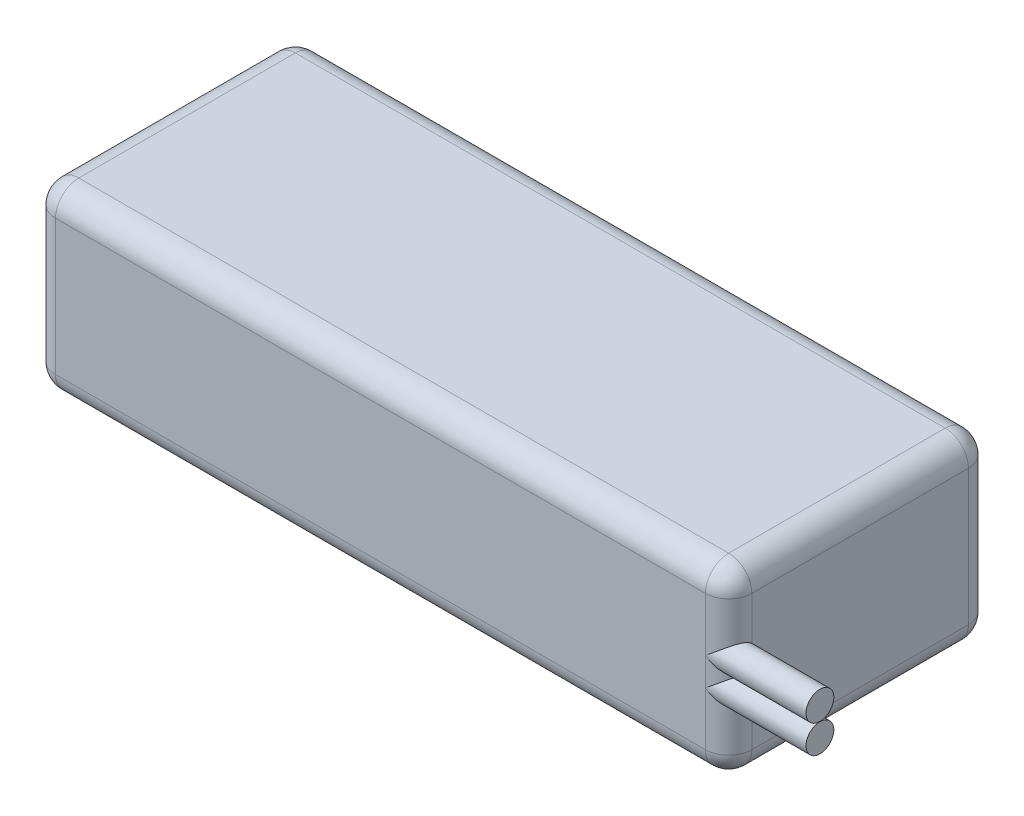
SolidWorks part; units mm, degrees
ref_plane "Front Plane" through (0, 0, 0) normal (0, 0, 1) x (1, 0, 0)
ref_plane "Top Plane" through (0, 0, 0) normal (0, 1, 0) x (1, 0, 0)
ref_plane "Right Plane" through (0, 0, 0) normal (1, 0, 0) x (0, 0, -1)
sketch "Sketch1" plane through (0, 0, 0) normal (0, 1, 0) x (1, 0, 0)
  line L1 (-42.6514, 15.3132) -> (47.3486, 15.3132)
  line L2 (-42.6514, 15.3132) -> (-42.6514, -18.6868)
  line L3 (-42.6514, -18.6868) -> (47.3486, -18.6868)
  line L4 (47.3486, 15.3132) -> (47.3486, -18.6868)
  dimension "D1" = 90
  dimension "D2" = 34
extrude "Boss-Extrude1" add sketch "Sketch1" along normal blind 23.5
sketch "Sketch2" plane through (47.3486, 0, 0) normal (1, 0, 0) x (0, 0, -1)
  line L0 (-18.6868, 23.5) -> (-18.6868, 0) construction
  line L1 (15.3132, 11.75) -> (-18.6868, 11.75) construction
  line L2 (15.3132, 23.5) -> (15.3132, 0) construction
  circle A0 centre (-16.8868, 13.57) radius 1.8
  circle A1 centre (-16.8868, 9.93) radius 1.8
  dimension "D1" = 3.6
  dimension "D2" = 1.82
  dimension "D3" = 1.82
extrude "Boss-Extrude4" add sketch "Sketch2" along normal blind 10
fillet "Fillet1" radius 3 14 edges at (-42.6514, 11.75, 18.6868) (47.3486, 18.535, 18.6868) (47.3486, 11.75, 18.6868) (47.3486, 4.965, 18.6868) (47.3486, 11.75, -15.3132) (-42.6514, 11.75, -15.3132) (2.3486, 23.5, -15.3132) (47.3486, 23.5, 1.6868) (2.3486, 23.5, 18.6868) (-42.6514, 23.5, 1.6868) (2.3486, 0, 18.6868) (47.3486, 0, 1.6868) (2.3486, 0, -15.3132) (-42.6514, 0, 1.6868)
